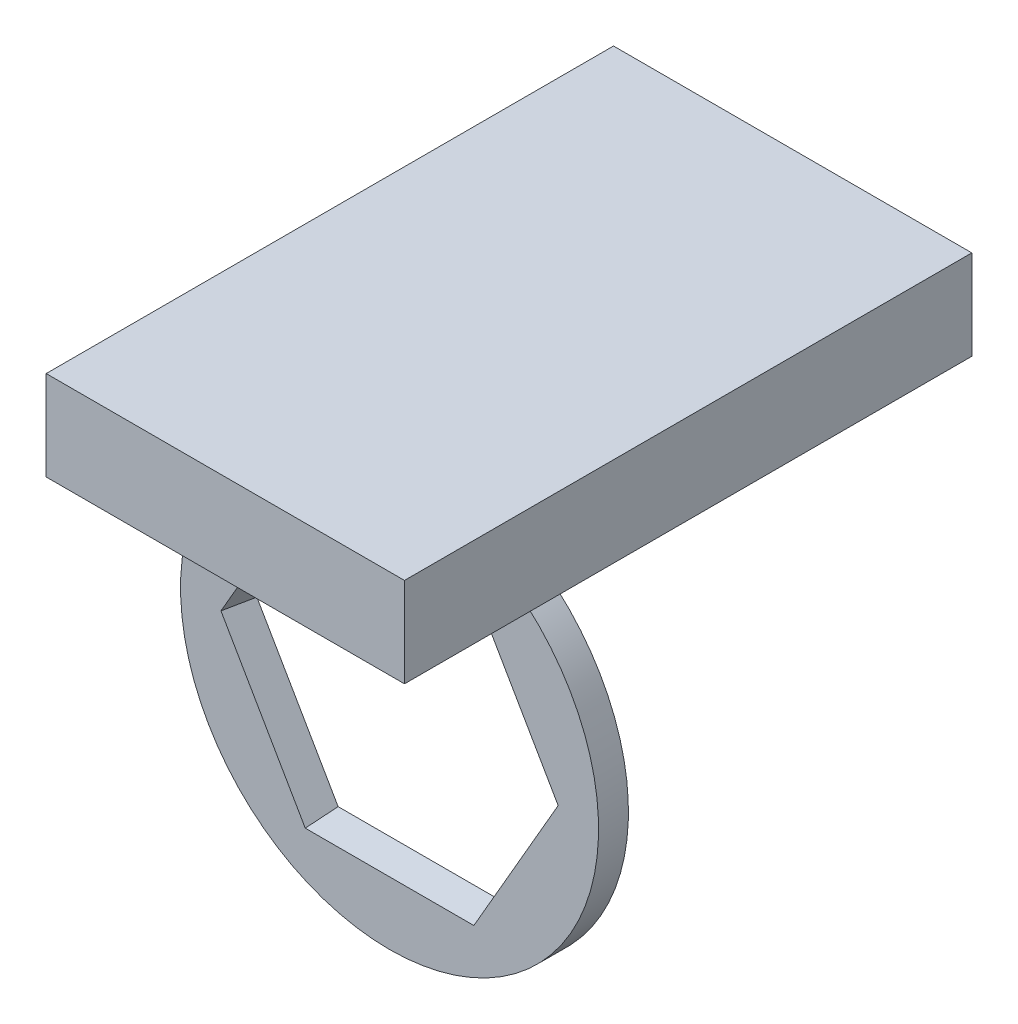
SolidWorks part; units mm, degrees
ref_plane "Plan de face" through (0, 0, 0) normal (0, 0, 1) x (1, 0, 0)
ref_plane "Plan de dessus" through (0, 0, 0) normal (0, 1, 0) x (1, 0, 0)
ref_plane "Plan de droite" through (0, 0, 0) normal (1, 0, 0) x (0, 0, -1)
sketch "Esquisse1" plane through (0, 0, 0) normal (0, 0, 1) x (1, 0, 0)
  line L1 (56.7939, 0) -> (28.397, 49.185)
  line L2 (28.397, 49.185) -> (-28.397, 49.185)
  line L3 (-28.397, 49.185) -> (-56.7939, 0)
  line L4 (-56.7939, 0) -> (-28.397, -49.185)
  line L5 (-28.397, -49.185) -> (28.397, -49.185)
  line L6 (28.397, -49.185) -> (56.7939, 0)
  circle A0 centre (0, 0) radius 70
  circle A1 centre (0, 0) radius 49.185 construction
  dimension "D1" = 140
  dimension "D2" = 98.37
extrude "Boss.-Extru.1" add sketch "Esquisse1" along normal blind 10
chamfer "Chanfrein1" distance 1.7471 angle 80.09 6 edges at (0, -49.185, 10) (42.5955, -24.5925, 10) (42.5955, 24.5925, 10) (0, 49.185, 10) (-42.5955, 24.5925, 10) (-42.5955, -24.5925, 10) first distance on face at (70, 0, 10)
other "Déplacer la face1" face at (-43.352, 25.0293, 5) face at (0, 50.0585, 5) face at (43.352, 25.0293, 5) face at (43.352, -25.0293, 5) face at (0, -50.0585, 5) face at (-43.352, -25.0293, 5) offset 2 parameters "D1"=2
ref_plane "Plan1" through (0, 94.5676, 0) normal (0, 1, 0) x (1, 0, 0)
sketch "Esquisse2" plane through (0, 94.5676, 0) normal (0, 1, 0) x (1, 0, 0)
  line L0 (-70, -10) -> (70, -10) construction
  line L1 (-60, 125) -> (60, 125)
  line L2 (-60, 125) -> (-60, -65)
  line L3 (-60, -65) -> (60, -65)
  line L4 (60, 125) -> (60, -65)
  line L5 (-70, -10) -> (70, -10) construction
  point P6 (-67.8934, -89.4149)
  point P7 (0, 125)
  point P8 (0, -10)
  dimension "D1" = 190
  dimension "D2" = 120
  dimension "D3" = 55
extrude "Boss.-Extru.2" add sketch "Esquisse2" against normal blind 30
